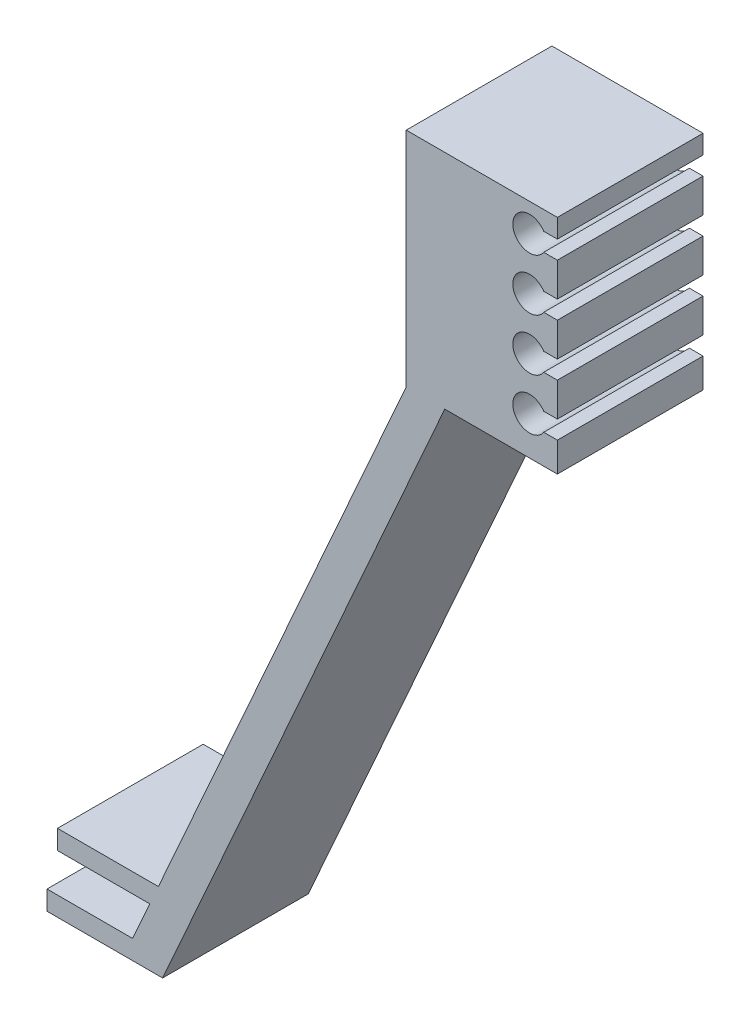
SolidWorks part; units mm, degrees
ref_plane "Front Plane" through (0, 0, 0) normal (0, 0, 1) x (1, 0, 0)
ref_plane "Top Plane" through (0, 0, 0) normal (0, 1, 0) x (1, 0, 0)
ref_plane "Right Plane" through (0, 0, 0) normal (1, 0, 0) x (0, 0, -1)
sketch "Sketch1" plane through (0, 0, 0) normal (0, 0, 1) x (1, 0, 0)
  line L2 (-159.7982, 9.1594) -> (-172.2482, 9.1594)
  line L3 (-172.2482, 9.1594) -> (-172.2482, -9.1594)
  line L7 (-169.2482, -22.8519) -> (-169.2482, 6.1594) construction
  line L13 (-142.8048, 5.1594) -> (-142.8048, -5.1594) construction
  line L23 (-159.7982, 6.1594) -> (-159.7982, 9.1594)
  line L28 (-164.5232, 5.2094) -> (-144.5007, 5.2094) construction
  line L30 (-169.2482, 6.1594) -> (-169.2482, 5.1594)
  line L34 (-169.2482, 5.1594) -> (-169.2482, -5.1594)
  line L35 (-172.2482, 0) -> (-169.2482, 0) construction
  line L36 (-169.2482, -6.1594) -> (-169.2482, -5.1594)
  line L37 (-159.7982, -6.1594) -> (-159.7982, -9.1594)
  line L38 (-159.7982, -9.1594) -> (-172.2482, -9.1594)
  arc A5 (-169.2482, 6.1594) -> (-159.7982, 6.1594) centre (-164.5232, 17.4347) ccw
  arc A6 (-169.2482, -6.1594) -> (-159.7982, -6.1594) centre (-164.5232, -17.4347) cw
  point P30 (-142.8048, 0)
  dimension "D6" = 12.2253
  dimension "D4" = 3
  dimension "D3" = 3
  dimension "D2" = 1
  dimension "D1" = 18.3188
  dimension "D5" = 12.45
extrude "MainBody" add sketch "Sketch1" along normal mid plane 12
sketch "Sketch3" plane through (0, -9.1594, 0) normal (0, -1, 0) x (1, 0, 0)
  line L0 (-159.7982, -6) -> (-161.8982, -7)
  line L1 (-161.8982, -7) -> (-161.8982, -6)
  line L2 (-172.2482, -6) -> (-159.7982, -6) construction
  line L3 (-161.8982, -6) -> (-159.7982, -6)
  line L5 (8.8033, 0) -> (-8.8033, 0) construction
  line L6 (-161.8982, 6) -> (-159.7982, 6)
  line L7 (-161.8982, 7) -> (-161.8982, 6)
  line L8 (-159.7982, 6) -> (-161.8982, 7)
  dimension "D1" = 2.1
  dimension "D2" = 1
extrude "Hook" [suppressed] add sketch "Sketch3" against normal up to vertex up to point (-159.7982, -6.1594, -6)
fillet "Fillet2" [suppressed] radius 1
sketch "Sketch5" [suppressed] plane through (-172.2482, 0, 0) normal (-1, 0, 0) x (0, 0, 1)
  line L1 (-6, 9.1594) -> (6, 9.1594)
  line L2 (-6, 9.1594) -> (-6, -9.1594)
  line L3 (-6, -9.1594) -> (6, -9.1594)
  line L4 (6, 9.1594) -> (6, -9.1594)
extrude "Boss-Extrude1" [suppressed] add sketch "Sketch5" along normal blind 15
sketch "Sketch6" [suppressed] plane through (0, 9.1594, 0) normal (0, 1, 0) x (1, 0, 0)
  line L0 (-187.2482, -6) -> (-187.2482, 6) construction
  circle A0 centre (-182.2482, 0) radius 3.302
  dimension "D1" = 6.604
  dimension "D2" = 5
extrude "Cut-Extrude2" [suppressed] cut sketch "Sketch6" against normal through all
sketch "Sketch7" plane through (-172.2482, 0, 0) normal (-1, 0, 0) x (0, 0, 1)
  circle A0 centre (0, 0) radius 38.1
  dimension "D1" = 76.2
extrude "Boss-Extrude2" [suppressed] add sketch "Sketch7" along normal blind 5
fillet "Fillet3" [suppressed] radius 1
sketch "Sketch8" plane through (0, 0, 6) normal (0, 0, 1) x (1, 0, 0)
  line L6 (-172.2482, -0.635) -> (-173.4343, -0.635)
  line L8 (-172.2482, 0.635) -> (-173.4343, 0.635)
  line L10 (-172.2482, 0.635) -> (-173.4343, 0.635)
  line L11 (-172.2482, 0.635) -> (-172.2482, -0.635)
  line L12 (-159.7982, -9.1594) -> (-159.7982, -6.1594)
  line L13 (-159.7982, -9.1594) -> (-159.7982, -6.1594)
  line L14 (-169.2482, -6.1594) -> (-169.2482, 6.1594)
  line L15 (-159.7982, 6.1594) -> (-159.7982, 9.1594)
  line L16 (-159.7982, 9.1594) -> (-172.2482, 9.1594)
  line L17 (-172.2482, 9.1594) -> (-172.2482, -9.1594)
  line L18 (-172.2482, -9.1594) -> (-159.7982, -9.1594)
  line L21 (-169.2482, -6.1594) -> (-169.2482, 6.1594)
  line L22 (-159.7982, 6.1594) -> (-159.7982, 9.1594)
  line L23 (-159.7982, 9.1594) -> (-172.2482, 9.1594)
  line L24 (-172.2482, 9.1594) -> (-172.2482, -9.1594)
  line L25 (-172.2482, -9.1594) -> (-159.7982, -9.1594)
  line L26 (-172.2482, -0.635) -> (-173.4343, -0.635)
  arc A0 (-173.4343, 0.635) -> (-173.4343, -0.635) centre (-174.5342, 0) ccw
  arc A4 (-159.7982, -6.1594) -> (-169.2482, -6.1594) centre (-164.5232, -17.4347) ccw
  arc A7 (-169.2482, 6.1594) -> (-159.7982, 6.1594) centre (-164.5232, 17.4347) ccw
  arc A8 (-159.7982, -6.1594) -> (-169.2482, -6.1594) centre (-164.5232, -17.4347) ccw
  arc A11 (-169.2482, 6.1594) -> (-159.7982, 6.1594) centre (-164.5232, 17.4347) ccw
  point P6 (-172.2482, 0)
  line M14 (-172.2482, 9.1594) -> (-172.2482, -9.1594)
  dimension "D2" = 1.27
  dimension "D1" = 0
  dimension "D3" = 2.286
extrude "Slot" [suppressed] add sketch "Sketch8" against normal up to surface (12 mm away) contours L8 A0 L6 M14 up to face at (-165.2732, 0, -6)
sketch "Sketch10" plane through (0, 0, -6) normal (0, 0, -1) x (-1, 0, 0)
  line L0 (166.0232, -9.1594) -> (172.2482, -9.1594)
  line L3 (172.2482, -9.1594) -> (166.0232, -9.1594)
  line L5 (172.2482, -9.1594) -> (187.9767, -44.4861)
  line L6 (195.4932, -61.3685) -> (192.3182, -61.3685)
  line L7 (159.7982, -6.1594) -> (159.7982, -9.1594)
  line L8 (159.7982, -6.1594) -> (159.7982, -9.1594)
  line L9 (159.7982, -9.1594) -> (172.2482, -9.1594)
  line L10 (172.2482, -9.1594) -> (172.2482, 9.1594)
  line L11 (172.2482, 9.1594) -> (159.7982, 9.1594)
  line L12 (159.7982, 9.1594) -> (159.7982, 6.1594)
  line L13 (169.2482, 6.1594) -> (169.2482, -6.1594)
  line L16 (159.7982, -9.1594) -> (172.2482, -9.1594)
  line L17 (172.2482, -9.1594) -> (172.2482, 9.1594)
  line L18 (172.2482, 9.1594) -> (159.7982, 9.1594)
  line L19 (159.7982, 9.1594) -> (159.7982, 6.1594)
  line L20 (169.2482, 6.1594) -> (169.2482, -6.1594)
  line L21 (195.4932, -61.3685) -> (201.8432, -61.3685)
  line L22 (201.8432, -61.3685) -> (201.8432, -59.781)
  line L24 (192.666, -55.0185) -> (200.9772, -55.0185)
  line L25 (169.0732, -9.1594) -> (192.3182, -61.3685)
  line L28 (201.8432, -59.781) -> (194.7864, -59.781)
  line L31 (193.3728, -56.606) -> (200.9772, -56.606)
  line L42 (200.9772, -55.0185) -> (200.9772, -56.606)
  line L43 (187.9767, -44.4861) -> (195.4932, -61.3685)
  arc A4 (169.2482, -6.1594) -> (159.7982, -6.1594) centre (164.5232, -17.4347) ccw
  arc A5 (159.7982, 6.1594) -> (169.2482, 6.1594) centre (164.5232, 17.4347) ccw
  arc A8 (169.2482, -6.1594) -> (159.7982, -6.1594) centre (164.5232, -17.4347) ccw
  arc A9 (159.7982, 6.1594) -> (169.2482, 6.1594) centre (164.5232, 17.4347) ccw
  line M18 (159.7982, -9.1594) -> (172.2482, -9.1594)
  dimension "D5" = 6.35
  dimension "D7" = 3.175
  dimension "D8" = 3.175
  dimension "D2" = 57.15
  dimension "D10" = 1.5875
  dimension "D13" = 114
  dimension "D14" = 114
  dimension "D3" = 1.5875
  dimension "D4" = 3.175
  dimension "D1" = 0
extrude "Boss-Extrude3" add sketch "Sketch10" against normal up to surface (12 mm away) contours L6 L5 M18 | L28 L43 L21 L22 | L43 | L43 | L43 | L43 L31 region at (-182.2832, -35.2639, -6) region at (-198.4884, -60.5608, -6) region at (-196.9956, -55.8005, -6) up to face at (-165.2732, 0, 6)
sketch "Sketch11" plane through (0, 0, -6) normal (0, 0, -1) x (-1, 0, 0)
  line L0 (159.7982, -9.1594) -> (159.7982, 9.1594)
  line L11 (169.2482, 6.1594) -> (169.2482, -6.1594)
  line L12 (159.7982, -6.1594) -> (159.7982, -9.1594)
  line L13 (159.7982, -9.1594) -> (169.0732, -9.1594)
  line L14 (169.0732, -9.1594) -> (192.3182, -61.3685)
  line L15 (192.3182, -61.3685) -> (201.8432, -61.3685)
  line L16 (201.8432, -61.3685) -> (201.8432, -59.781)
  line L17 (201.8432, -59.781) -> (194.7864, -59.781)
  line L18 (194.7864, -59.781) -> (193.3728, -56.606)
  line L19 (172.2482, -9.1594) -> (172.2482, 9.1594)
  line L20 (172.2482, 9.1594) -> (159.7982, 9.1594)
  line L21 (159.7982, 9.1594) -> (159.7982, 6.1594)
  line L22 (169.2482, 6.1594) -> (169.2482, -6.1594)
  line L23 (159.7982, -6.1594) -> (159.7982, -9.1594)
  line L24 (159.7982, -9.1594) -> (169.0732, -9.1594)
  line L25 (169.0732, -9.1594) -> (192.3182, -61.3685)
  line L26 (192.3182, -61.3685) -> (201.8432, -61.3685)
  line L27 (201.8432, -61.3685) -> (201.8432, -59.781)
  line L28 (201.8432, -59.781) -> (194.7864, -59.781)
  line L29 (194.7864, -59.781) -> (193.3728, -56.606)
  line L30 (172.2482, -9.1594) -> (172.2482, 9.1594)
  line L31 (172.2482, 9.1594) -> (159.7982, 9.1594)
  line L32 (159.7982, 9.1594) -> (159.7982, 6.1594)
  line L37 (193.3728, -56.606) -> (200.9772, -56.606)
  line L38 (193.3728, -56.606) -> (200.9772, -56.606)
  line L39 (200.9772, -56.606) -> (200.9772, -55.0185)
  line L40 (200.9772, -56.606) -> (200.9772, -55.0185)
  line L41 (192.666, -55.0185) -> (172.2482, -9.1594)
  line L42 (192.666, -55.0185) -> (172.2482, -9.1594)
  line L44 (200.9772, -55.0185) -> (192.666, -55.0185)
  line L45 (200.9772, -55.0185) -> (192.666, -55.0185)
  arc A2 (159.7982, 6.1594) -> (169.2482, 6.1594) centre (164.5232, 17.4347) ccw
  arc A3 (169.2482, -6.1594) -> (159.7982, -6.1594) centre (164.5232, -17.4347) ccw
  arc A4 (159.7982, 6.1594) -> (169.2482, 6.1594) centre (164.5232, 17.4347) ccw
  arc A5 (169.2482, -6.1594) -> (159.7982, -6.1594) centre (164.5232, -17.4347) ccw
  arc M14 (159.7982, 6.1594) -> (169.2482, 6.1594) centre (164.5232, 17.4347) ccw
  line M15 (169.2482, 6.1594) -> (169.2482, -6.1594)
  arc M16 (169.2482, -6.1594) -> (159.7982, -6.1594) centre (164.5232, -17.4347) ccw
  dimension "D1" = 0
extrude "Boss-Extrude4" add sketch "Sketch11" against normal up to surface (12 mm away) contours L0 M16 M15 M14 region at (-164.5232, 0, -6) up to face at (-180.5907, -27.924, 6)
sketch "Sketch12" plane through (0, 0, -6) normal (0, 0, -1) x (-1, 0, 0)
  line L0 (159.7982, -9.1594) -> (159.7982, -5.9844)
  line L1 (159.7982, -5.9844) -> (162.0842, -5.9844)
  line L3 (162.0842, -5.2351) -> (159.7982, -5.2351)
  line L4 (162.0842, -5.2351) -> (162.0842, -6.7337)
  line L5 (162.0842, -6.7337) -> (159.7982, -6.7337)
  line L6 (159.7982, -5.2351) -> (159.7982, -6.7337)
  line L7 (162.0842, -5.2351) -> (159.7982, -6.7337) construction
  line L8 (162.0842, -6.7337) -> (159.7982, -5.2351) construction
  line L9 (172.2482, 9.1594) -> (159.7982, 9.1594)
  line L10 (159.7982, 9.1594) -> (159.7982, -9.1594)
  line L11 (159.7982, -9.1594) -> (169.0732, -9.1594)
  line L12 (169.0732, -9.1594) -> (192.3182, -61.3685)
  line L13 (192.3182, -61.3685) -> (201.8432, -61.3685)
  line L14 (201.8432, -61.3685) -> (201.8432, -59.781)
  line L15 (201.8432, -59.781) -> (194.7864, -59.781)
  line L16 (194.7864, -59.781) -> (193.3728, -56.606)
  line L17 (172.2482, -9.1594) -> (172.2482, 9.1594)
  line L18 (172.2482, 9.1594) -> (159.7982, 9.1594)
  line L19 (159.7982, 9.1594) -> (159.7982, -9.1594)
  line L20 (159.7982, -9.1594) -> (169.0732, -9.1594)
  line L21 (169.0732, -9.1594) -> (192.3182, -61.3685)
  line L22 (192.3182, -61.3685) -> (201.8432, -61.3685)
  line L23 (201.8432, -61.3685) -> (201.8432, -59.781)
  line L24 (201.8432, -59.781) -> (194.7864, -59.781)
  line L25 (194.7864, -59.781) -> (193.3728, -56.606)
  line L26 (172.2482, -9.1594) -> (172.2482, 9.1594)
  line L38 (193.3728, -56.606) -> (200.9772, -56.606)
  line L39 (193.3728, -56.606) -> (200.9772, -56.606)
  line L40 (200.9772, -56.606) -> (200.9772, -55.0185)
  line L42 (192.666, -55.0185) -> (172.2482, -9.1594)
  line L43 (192.666, -55.0185) -> (172.2482, -9.1594)
  line L45 (200.9772, -56.606) -> (200.9772, -55.0185)
  line L46 (200.9772, -55.0185) -> (192.666, -55.0185)
  line L47 (200.9772, -55.0185) -> (192.666, -55.0185)
  circle A0 centre (162.0842, -5.9844) radius 1.3843
  point P8 (160.9412, -5.9844)
  line M13 (159.7982, 9.1594) -> (159.7982, -9.1594)
  dimension "D1" = 0
  dimension "D4" = 2.7686
  dimension "D2" = 3.175
  dimension "D3" = 2.286
  dimension "D5" = 1.4986
extrude "Cut-Extrude3" cut sketch "Sketch12" against normal up to surface (12 mm away) contours L5 A0 L3 L4 | L1 A0 L5 L4 | A0 L1 L5 M13 | L3 A0 L1 L4 | A0 L3 L1 M13 region at (-160.2867, -6.3729, -6) region at (-160.2867, -5.5958, -6) region at (-161.4259, -6.3487, -6) region at (-162.4039, -5.9844, -6) region at (-161.4259, -5.62, -6) up to face at (-185.5346, -36.516, 6)
pattern_linear "LPattern1" count 4 spacing 4.28 along (0, 1, 0) of "Cut-Extrude3"
equation "\"HookThickness\"= 3mm"
equation "\"D3@Sketch1\"=\"HookThickness\""
equation "\"D4@Sketch1\"=\"HookThickness\""
equation "\"CylinderDiameter\"=3"
equation "\"D1@Sketch7\"=\"CylinderDiameter\""
equation "\"Mount Tolerance\"= .005in"
equation "\"Mount Thickness\"= .0625in"
equation "\"Mount Angle\"= 114"
equation "\"D14@Sketch10\"=\"Mount Angle\""
equation "\"D13@Sketch10\"= \"Mount Angle\""
equation "\"Joint Radius\"= .05in"
equation "\"Joint Thickness\"= .05in"
equation "\"Joint Tolerance\"= .009in"
equation "\"D4@Sketch12\"= (\"Joint Radius\" * 2) + \"Joint Tolerance\""
equation "\"D5@Sketch12\"= \"Joint Thickness\" + \"Joint Tolerance\""
